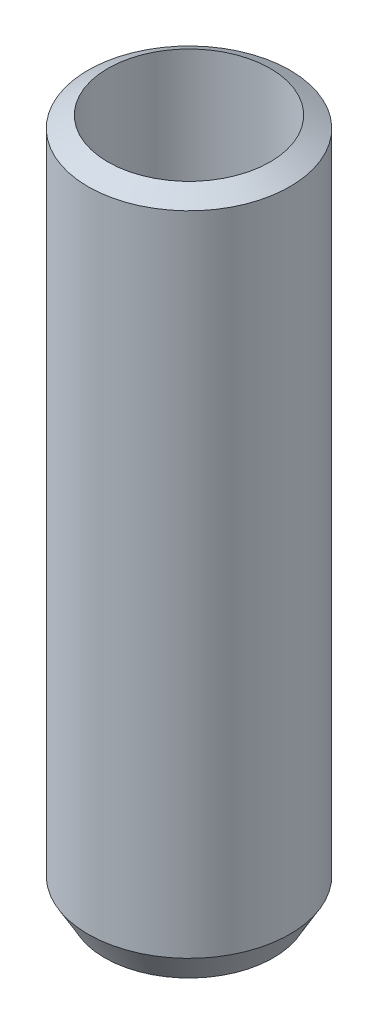
SolidWorks part; units mm, degrees
ref_plane "Front Plane" through (0, 0, 0) normal (0, 0, 1) x (1, 0, 0)
ref_plane "Top Plane" through (0, 0, 0) normal (0, 1, 0) x (1, 0, 0)
ref_plane "Right Plane" through (0, 0, 0) normal (1, 0, 0) x (0, 0, -1)
sketch "Sketch1" plane through (0, 0, 0) normal (0, 1, 0) x (1, 0, 0)
  circle A0 centre (0, 0) radius 35
  dimension "SHAFT_OD" = 70
extrude "Boss-Extrude1" add sketch "Sketch1" along normal blind 240.2181
sketch "Sketch2" plane through (0, 0, 0) normal (0, 1, 0) x (1, 0, 0)
  circle A0 centre (0, 0) radius 28.1205
  dimension "BORE_D" = 56.241
extrude "Cut-Extrude1" cut sketch "Sketch2" along normal through all
chamfer "Chamfer1" distance 5.77 angle 60 2 edges at (0, 240.2181, 35) (0, 0, 35) first distance on face at (0, 240.2181, 35) first distance on face at (0, 0, 28.1205)
